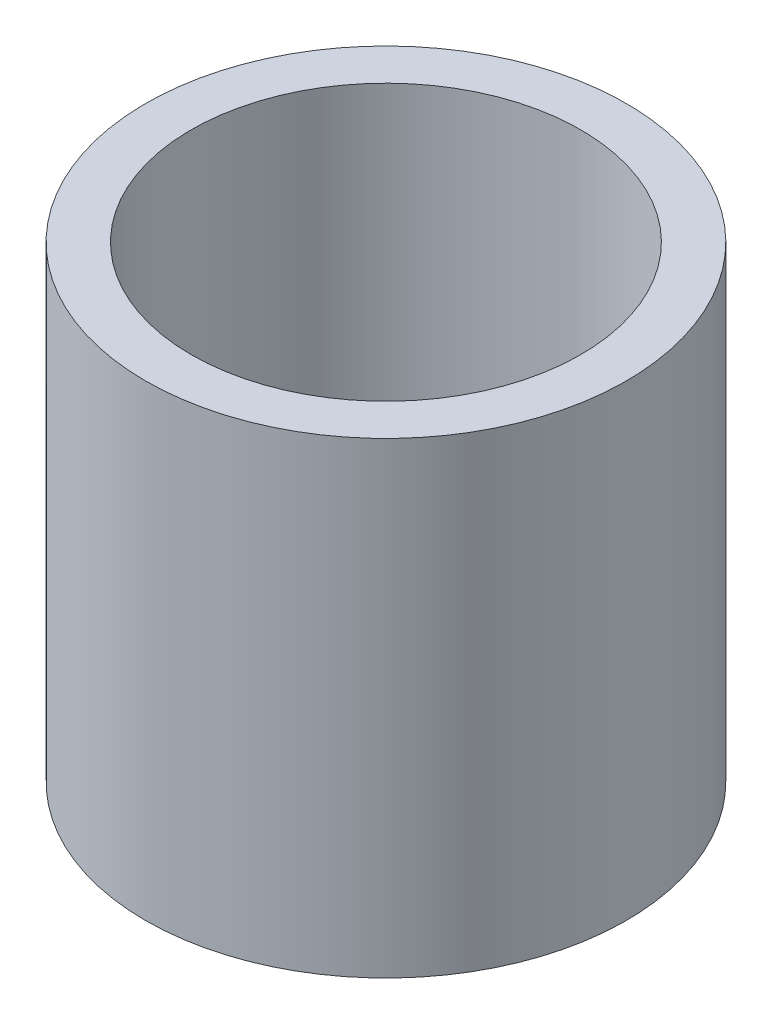
SolidWorks part; units mm, degrees
ref_plane "Front Plane" through (0, 0, 0) normal (0, 0, 1) x (1, 0, 0)
ref_plane "Top Plane" through (0, 0, 0) normal (0, 1, 0) x (1, 0, 0)
ref_plane "Right Plane" through (0, 0, 0) normal (1, 0, 0) x (0, 0, -1)
sketch "Sketch1" plane through (0, 0, 0) normal (0, 1, 0) x (1, 0, 0)
  circle A0 centre (0, 0) radius 52.5
  dimension "SLEEVE_OD" = 105
extrude "Boss-Extrude1" add sketch "Sketch1" along normal blind 102.0846
sketch "Sketch2" plane through (0, 0, 0) normal (0, 1, 0) x (1, 0, 0)
  circle A0 centre (0, 0) radius 42.5524
  dimension "BORE_D" = 85.1048
extrude "Cut-Extrude1" cut sketch "Sketch2" along normal through all
chamfer "Chamfer1" distance 3.906 angle 60 rebuild error yes
